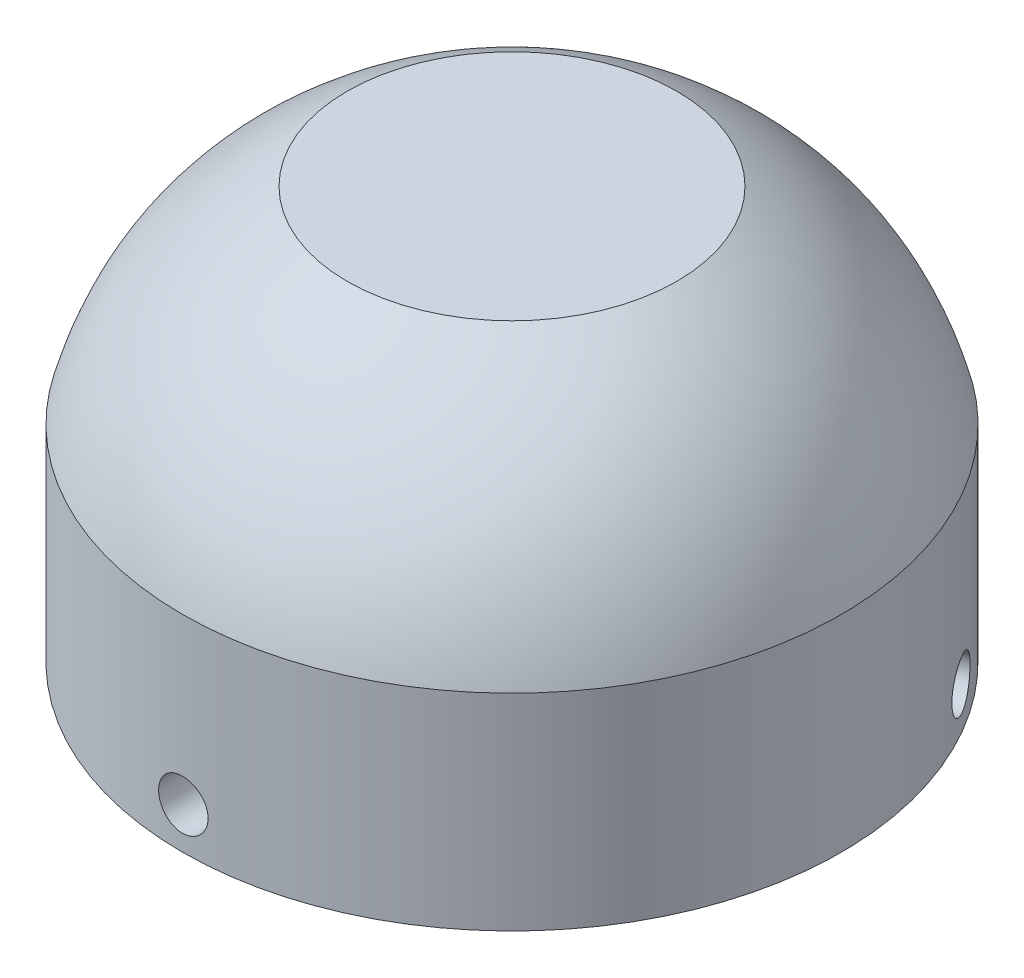
SolidWorks part; units mm, degrees
ref_plane "Front Plane" through (0, 0, 0) normal (0, 0, 1) x (1, 0, 0)
ref_plane "Top Plane" through (0, 0, 0) normal (0, 1, 0) x (1, 0, 0)
ref_plane "Right Plane" through (0, 0, 0) normal (1, 0, 0) x (0, 0, -1)
sketch "Sketch1" plane through (0, 0, 0) normal (0, 0, 1) x (1, 0, 0)
  line L0 (15.999, 0) -> (20.999, 0) construction
  line L1 (0, -63.9535) -> (0, 73.7209) construction
  line L2 (-20, 30) -> (0, 30)
  line L3 (0, 30) -> (0, 22.9289)
  line L4 (0, 22.9289) -> (-20, 22.9289)
  line L5 (-35, 0) -> (-40, 0) construction
  line L6 (-40, 0) -> (-40, 5)
  line L7 (-35, 0) -> (-35, -20)
  line L8 (-35, -20) -> (-40, -20)
  line L9 (-40, -20) -> (-40, 0)
  line L10 (-20, 30) -> (-20, 22.9289) construction
  line L11 (-35, 0) -> (-40, 5) construction
  line L12 (-40, 5) -> (-32.1, 9.7538) construction
  line L13 (-32.1, 9.7538) -> (-32.1, 20.5) construction
  spline S0 degree 2 poles (-20, 30) (-35.4489, 21.9814) (-40, 5) knots 0 0 0 1 1 1
  spline S1 degree 2 poles (-20, 22.9289) (-32.9925, 14.5797) (-35, 0) knots 0 0 0 1 1 1
  point P16 (-32.1, 20.5)
  dimension "D1" = 20
  dimension "D2" = 30
  dimension "D3" = 5
  dimension "D4" = 15.5
  dimension "D5" = 7.9
  dimension "D6" = 40
  dimension "D7" = 5
  dimension "D8" = 9.22
  dimension "D9" = 20
revolve "Revolve1" add sketch "Sketch1" angle 360 about L1
ref_plane "Plane1" through (0, 0, 40) normal (0, 0, 1) x (1, 0, 0)
sketch "Sketch2" plane through (0, 0, 40) normal (0, 0, 1) x (1, 0, 0)
  line L0 (0, -27.9441) -> (0, 37.3854) construction
  line L1 (-40, -20) -> (40, -20) construction
  line L2 (-40, -20) -> (40, -20) construction
  circle A0 centre (0, -15) radius 3
  dimension "D2" = 6
  dimension "D1" = 5
extrude "Cut-Extrude1" cut sketch "Sketch2" against normal up to next
pattern_circular "CirPattern1" count 3 over 360 about axis through (0, 5, 0) along (0, -1, 0) of "Cut-Extrude1"
